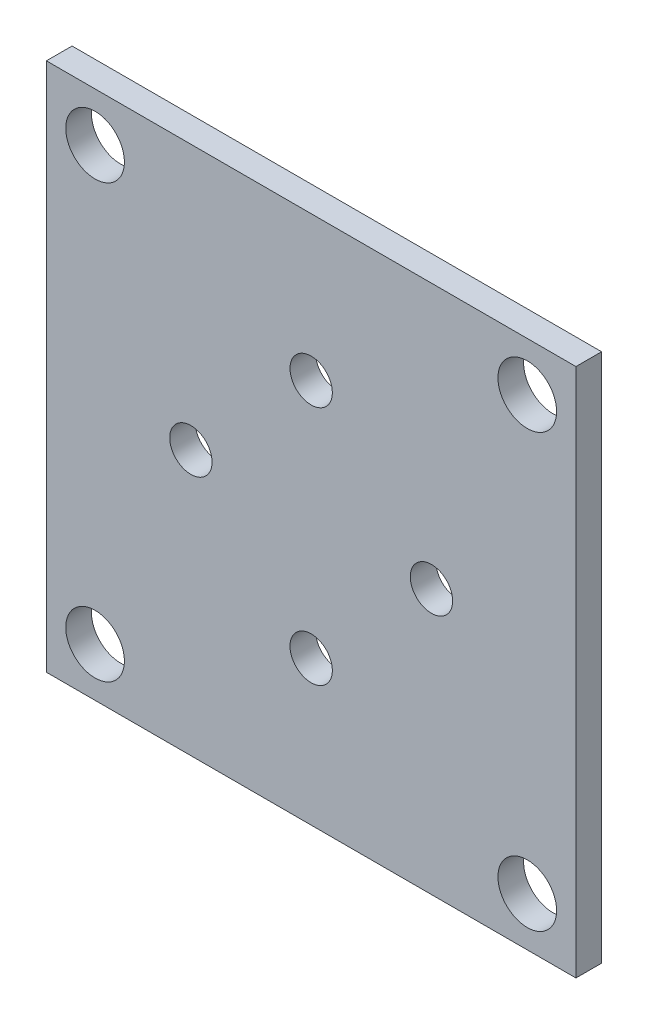
SolidWorks part; units mm, degrees
material "6061 Alloy"
ref_plane "Front Plane" through (0, 0, 0) normal (0, 0, 1) x (1, 0, 0)
ref_plane "Top Plane" through (0, 0, 0) normal (0, 1, 0) x (1, 0, 0)
ref_plane "Right Plane" through (0, 0, 0) normal (1, 0, 0) x (0, 0, -1)
sketch "Sketch1" plane through (0, 0, 0) normal (0, 0, 1) x (1, 0, 0)
  line L1 (-16.51, -16.51) -> (16.51, -16.51)
  line L2 (-16.51, -16.51) -> (-16.51, 16.51)
  line L3 (-16.51, 16.51) -> (16.51, 16.51)
  line L4 (16.51, -16.51) -> (16.51, 16.51)
  line L5 (-16.51, -16.51) -> (16.51, 16.51) construction
  line L6 (-16.51, 16.51) -> (16.51, -16.51) construction
  point P0 (0, 0)
  dimension "D1" = 33.02
extrude "Boss-Extrude1" add sketch "Sketch1" along normal blind 1.6002
hole_wizard "#27 (0.144) Diameter Hole1" positions "Sketch3" profile "Sketch2" hole size "#27" standard "ANSI Inch" end condition through all
sketch "Sketch3" plane through (0, 0, 1.6002) normal (0, 0, 1) x (1, 0, 0)
  line L0 (-13.4747, 13.4747) -> (-13.4747, -13.4747) construction
  line L1 (-13.4747, -13.4747) -> (13.4747, -13.4747) construction
  line L2 (13.4747, -13.4747) -> (13.4747, 13.4747) construction
  line L3 (13.4747, 13.4747) -> (-13.4747, 13.4747) construction
  line L5 (13.4747, 0) -> (16.51, 0) construction
  line L6 (16.51, -16.51) -> (16.51, 16.51) construction
  line L9 (0, 13.4747) -> (0, 16.51) construction
  line L10 (16.51, 16.51) -> (-16.51, 16.51) construction
  point P0 (-13.4747, 13.4747)
  point P2 (13.4747, 13.4747)
  point P4 (13.4747, -13.4747)
  point P6 (-13.4747, -13.4747)
  dimension "D1" = 26.9494
sketch "Sketch2" plane through (-13.4747, 13.4747, 1.6002) normal (1, 0, 0) x (0, -1, 0)
  line L0 (0, 0) -> (0, 1.6002)
  line L1 (0, 1.6002) -> (1.8288, 1.6002)
  line L2 (1.8288, 1.6002) -> (1.8288, 0)
  line L5 (1.8288, 0) -> (0, 0)
  line L11 (0, -6.35) -> (0, 107.95) construction
  dimension "Thru Hole Dia." = 3.6576
  dimension "Thru Hole Depth" = 1.6002
hole_wizard "#37 (0.104) Diameter Hole1" positions "Sketch5" profile "Sketch4" hole size "#37" standard "ANSI Inch" end condition through all
sketch "Sketch5" plane through (0, 0, 1.6002) normal (0, 0, 1) x (1, 0, 0)
  line L0 (0, 7.5) -> (0, -7.5) construction
  line L3 (7.5, 0) -> (-7.5, 0) construction
  point P0 (0, 7.5)
  point P2 (7.5, 0)
  point P4 (0, -7.5)
  point P6 (-7.5, 0)
  dimension "D1" = 15
sketch "Sketch4" plane through (0, 7.5, 1.6002) normal (1, 0, 0) x (0, -1, 0)
  line L0 (0, 0) -> (0, 1.6002)
  line L1 (0, 1.6002) -> (1.3208, 1.6002)
  line L2 (1.3208, 1.6002) -> (1.3208, 0)
  line L5 (1.3208, 0) -> (0, 0)
  line L11 (0, -6.35) -> (0, 107.95) construction
  dimension "Thru Hole Dia." = 2.6416
  dimension "Thru Hole Depth" = 1.6002
